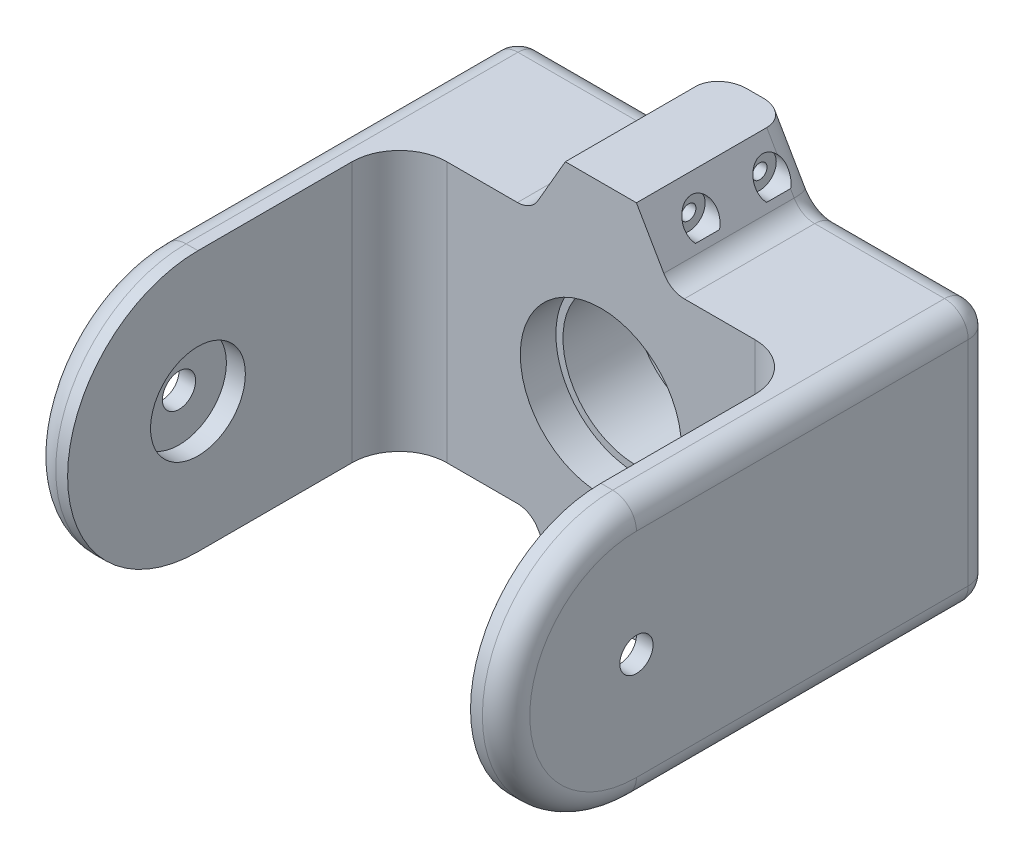
SolidWorks part; units mm, degrees
ref_plane "Front Plane" through (0, 0, 0) normal (0, 0, 1) x (1, 0, 0)
ref_plane "Top Plane" through (0, 0, 0) normal (0, 1, 0) x (1, 0, 0)
ref_plane "Right Plane" through (0, 0, 0) normal (1, 0, 0) x (0, 0, -1)
sketch "Sketch1" plane through (0, 0, 0) normal (0, 0, 1) x (1, 0, 0)
  circle A2 centre (0, 0) radius 34
  circle A3 centre (0, 0) radius 34 construction
  circle A4 centre (0, 0) radius 31
  circle A5 centre (0, 0) radius 30 construction
  dimension "D1" = 1
extrude "Centre Hole for L2" add sketch "Sketch1" along normal blind 30 contours A4 | A2
sketch "Sketch2" plane through (0, 0, 30) normal (0, 0, 1) x (1, 0, 0)
  line L0 (0, 48.4974) -> (0, 0) construction
  line L5 (-100, 55) -> (-100, -55)
  line L12 (0, 0) -> (72.986, 0) construction
  line L16 (-100, 55) -> (100, 55)
  line L17 (100, 55) -> (100, -55)
  line L18 (-100, -55) -> (100, -55)
  circle A0 centre (0, 0) radius 34
  circle A1 centre (0, 0) radius 34 construction
  circle A5 centre (0, 0) radius 34
  point P13 (0, 55)
  dimension "D1" = 100
  dimension "D2" = 110
extrude "Main Structure" add sketch "Sketch2" along normal blind 100 and the other way blind 50 separate body contours L5 L18 L17 L16 | A5
sketch "Sketch3" plane through (-100, 0, 0) normal (-1, 0, 0) x (0, 0, 1)
  line L0 (130, 55) -> (130, -55) construction
  line L1 (130, 55) -> (130, -55)
  line L2 (-20, 55) -> (130, 55) construction
  arc A0 (130, 55) -> (130, -55) centre (130, 0) cw
extrude "Bearing Curve" add sketch "Sketch3" against normal blind 15 contours A0 L1
mirror "Mirror7" about plane through (0, 0, 0) normal (1, 0, 0) of "Bearing Curve"
sketch "Sketch6" plane through (-100, 0, 0) normal (-1, 0, 0) x (0, 0, 1)
  circle A0 centre (130, 0) radius 7
  dimension "D1" = 14
extrude "Cut-Extrude2" cut sketch "Sketch6" against normal up to surface (15 mm away) up to face at (-85, 0, 157.5)
sketch "Sketch4" plane through (0, 55, 0) normal (0, 1, 0) x (1, 0, 0)
  line L0 (0, -110) -> (0, 20) construction
  line L1 (-85, -130) -> (85, -130) construction
  line L2 (-100, 20) -> (100, 20) construction
  line L3 (-85, -130) -> (-85, -65)
  line L4 (-65, -45) -> (65, -45)
  line L5 (-85, -130) -> (85, -130)
  line L6 (85, -130) -> (85, -65)
  arc A0 (-85, -65) -> (-65, -45) centre (-65, -65) cw
  arc A1 (85, -65) -> (65, -45) centre (65, -65) ccw
  point P17 (0, -130)
  point P20 (0, -45)
  dimension "D2" = 20
  dimension "D1" = 65
extrude "Wrist Cutout" cut sketch "Sketch4" against normal through all
sketch "Sketch9" plane through (-85, 0, 0) normal (1, 0, 0) x (0, 0, -1)
  circle A0 centre (-130, 0) radius 20
  dimension "D1" = 40
extrude "Cut-Extrude3" cut sketch "Sketch9" against normal blind 8
mirror "Mirror6" about plane through (0, 0, 0) normal (1, 0, 0) of "Cut-Extrude2", "Cut-Extrude3"
fillet "Fillet2" radius 10 2 edges at (-100, 0, -20) (100, 0, -20)
sketch "Sketch10" plane through (0, 0, -20) normal (0, 0, -1) x (-1, 0, 0)
  line L0 (0, 55) -> (0, 80) construction
  line L1 (90, 55) -> (-90, 55) construction
  line L2 (15, 80) -> (-15, 80)
  line L3 (-15, 80) -> (-29.4338, 55)
  line L4 (-29.4338, 55) -> (29.4338, 55)
  line L5 (15, 80) -> (29.4338, 55)
  dimension "D1" = 25
  dimension "D2" = 15
  dimension "D3" = 60
extrude "Boss-Extrude4" add sketch "Sketch10" against normal up to surface (65 mm away) up to face at (0, 0, 45)
sketch "Sketch11" plane through (0, 0, 0) normal (1, 0, 0) x (0, 0, -1)
  line L1 (-45, 67.5) -> (20, 67.5) construction
  line L2 (-45, 55) -> (-45, 80) construction
  line L3 (20, 80) -> (20, 55) construction
  circle A1 centre (5, 67.5) radius 3.1
  circle A2 centre (-25, 67.5) radius 3.1
  dimension "D1" = 6.2
  dimension "D2" = 15
  dimension "D3" = 30
extrude "Cut-Extrude6" cut sketch "Sketch11" against normal through all both and the other way through all
sketch "Sketch13" plane through (0, 0, 0) normal (1, 0, 0) x (0, 0, -1)
  circle A0 centre (5, 67.5) radius 7
  circle A1 centre (-25, 67.5) radius 7
  dimension "D1" = 14
extrude "Cut-Extrude8" cut sketch "Sketch13" against normal blind 8 from offset 25
mirror "Mirror8" about plane through (0, 0, 0) normal (0, 1, 0) of "Cut-Extrude6", "Cut-Extrude8", "Boss-Extrude4"
fillet "Fillet3" radius 10 4 edges at (-29.4338, -55, 12.5) (29.4338, -55, 12.5) (-29.4338, 55, 12.5) (29.4338, 55, 12.5)
fillet "Fillet1" radius 10 22 edges at (-100, 55, 60) (-100, -55, 60) (100, -55, 60) (100, 55, 60) (-100, 0, 185) (-20.7735, -70, -20) (-30.2073, -56.3397, -20) (-62.6036, -55, -20) (-97.0711, -55, -17.0711) (-20.7735, 70, -20) (-30.2073, 56.3397, -20) (-62.6036, 55, -20) (-97.0711, 55, -17.0711) (20.7735, 70, -20) (30.2073, 56.3397, -20) (62.6036, 55, -20) (97.0711, 55, -17.0711) (20.7735, -70, -20) (30.2073, -56.3397, -20) (62.6036, -55, -20) (97.0711, -55, -17.0711) (100, 0, 185)
